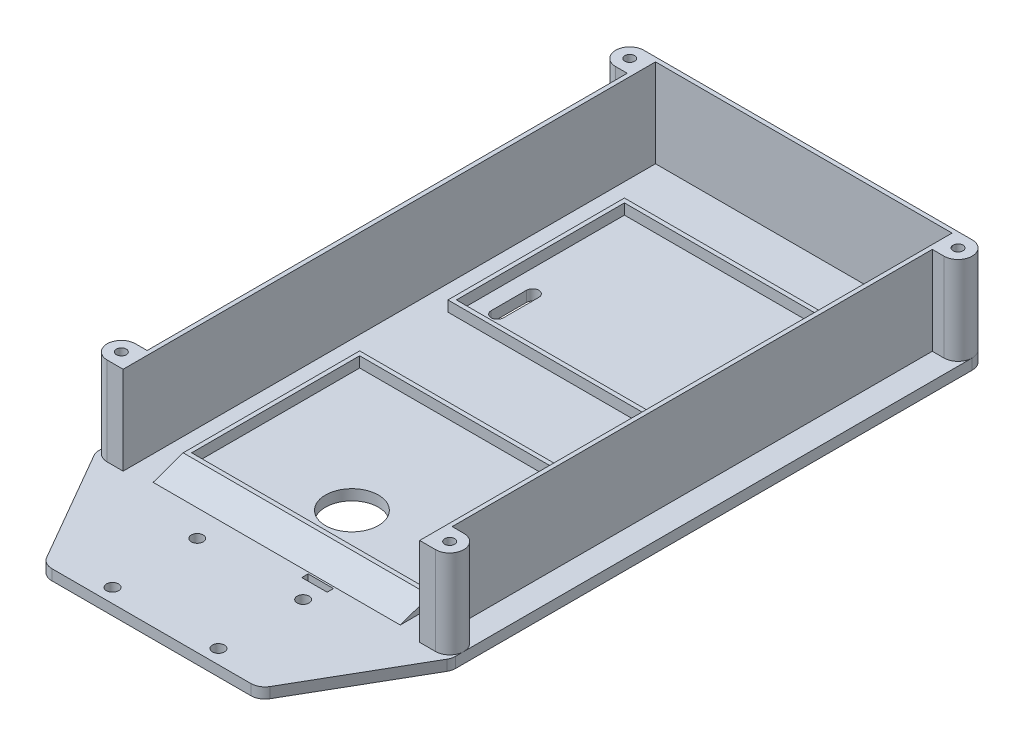
SolidWorks part; units mm, degrees
material "S235JR"
ref_plane "Piano X" through (0, 0, 0) normal (0, 0, 1) x (1, 0, 0)
ref_plane "Piano Y" through (0, 0, 0) normal (0, 1, 0) x (1, 0, 0)
ref_plane "Piano Z" through (0, 0, 0) normal (1, 0, 0) x (0, 0, -1)
sketch "Schizzo1" plane through (0, 0, 0) normal (0, 1, 0) x (1, 0, 0)
  line L1 (-50.5, -93) -> (50.5, -93)
  line L2 (-50.5, -93) -> (-50.5, 93)
  line L3 (-50.5, 93) -> (50.5, 93)
  line L4 (50.5, -93) -> (50.5, 93)
  line L5 (0, 93) -> (0, -93) construction
  line L6 (-50.5, 0) -> (50.5, 0) construction
  point P0 (0, 0)
  dimension "D2" = 101
  dimension "D3" = 186
extrude "Estrusione-Estrusione1" add sketch "Schizzo1" along normal blind 3
sketch "Schizzo3" plane through (0, 3, 0) normal (0, 1, 0) x (1, 0, 0)
  line L0 (-43.2, -59) -> (-42, -59)
  line L1 (42, 91.8) -> (-42, 91.8)
  line L2 (42, 91.8) -> (42, -59)
  line L4 (-42, 91.8) -> (-42, -59)
  line L5 (0, 86.851) -> (0, 91.8) construction
  line L6 (42, 16.4) -> (-42, 16.4) construction
  line L7 (43.2, 93) -> (-43.2, 93)
  line L8 (43.2, 93) -> (43.2, -59)
  line L10 (-43.2, 93) -> (-43.2, -59)
  line L11 (0, 88.051) -> (0, 93) construction
  line L12 (43.2, 16.4) -> (-43.2, 16.4) construction
  line L13 (42, -59) -> (43.2, -59)
  line L14 (-50.5, -93) -> (50.5, -93) construction
  point P0 (0, 16.4)
  point P4 (0, 16.4)
  point P11 (43.2, 75.8551)
  point P12 (0, 0)
  point P13 (-42, -72.5522)
  point P19 (0, 0)
  dimension "D1" = 84
  dimension "D2" = 1.2
  dimension "D3" = 1.2
  dimension "D4" = 34
  dimension "D5" = 152
extrude "Estrusione-Estrusione3" add sketch "Schizzo3" along normal blind 25
sketch "Schizzo2" plane through (0, 3, 0) normal (0, 1, 0) x (1, 0, 0)
  line L0 (0, 51) -> (0, -24) construction
  line L1 (35, 26) -> (-35, 26)
  line L2 (35, 26) -> (35, 76)
  line L3 (35, 76) -> (-35, 76)
  line L4 (-35, 26) -> (-35, 76)
  line L5 (0, 76) -> (0, 26) construction
  line L6 (35, 51) -> (-35, 51) construction
  line L7 (33.8, 27.2) -> (-33.8, 27.2)
  line L8 (33.8, 27.2) -> (33.8, 74.8)
  line L9 (33.8, 74.8) -> (-33.8, 74.8)
  line L10 (-33.8, 27.2) -> (-33.8, 74.8)
  line L11 (0, 74.8) -> (0, 27.2) construction
  line L12 (33.8, 51) -> (-33.8, 51) construction
  line L13 (33.8, -47.8) -> (-33.8, -47.8)
  line L14 (33.8, -47.8) -> (33.8, -0.2)
  line L15 (33.8, -0.2) -> (-33.8, -0.2)
  line L16 (-33.8, -47.8) -> (-33.8, -0.2)
  line L17 (0, -0.2) -> (0, -47.8) construction
  line L18 (33.8, -24) -> (-33.8, -24) construction
  line L19 (35, -49) -> (-35, -49)
  line L20 (35, -49) -> (35, 1)
  line L21 (35, 1) -> (-35, 1)
  line L22 (-35, -49) -> (-35, 1)
  line L23 (0, 1) -> (0, -49) construction
  line L24 (35, -24) -> (-35, -24) construction
  point P0 (0, 51)
  point P4 (0, 51)
  point P11 (0, -24)
  point P18 (0, -24)
  point P25 (15.7007, -24.3129)
  point P26 (0, 0)
  point P32 (0, 0)
  point P33 (0, 0)
  point P34 (0, 0)
  dimension "D1" = 1.2
  dimension "D2" = 1.2
  dimension "D3" = 70
  dimension "D4" = 50
  dimension "D5" = 10
  dimension "D6" = 25
extrude "Estrusione-Estrusione2" add sketch "Schizzo2" along normal blind 3
sketch "Schizzo13" plane through (-35, 0, 0) normal (-1, 0, 0) x (0, 0, 1)
  line L0 (49, 6) -> (57.5, 3)
  line L1 (57.5, 3) -> (49, 3)
  line L2 (49, 3) -> (49, 6)
  line L3 (-93, 3) -> (93, 3) construction
  line L4 (59, 28) -> (59, 3) construction
  point P4 (57.5991, 3)
  dimension "D1" = 1.5
extrude "Estrusione-Estrusione5" add sketch "Schizzo13" against normal up to surface (70 mm away) up to face at (35, 4.5, 24)
sketch "Schizzo9" plane through (0, 3, 0) normal (0, 1, 0) x (1, 0, 0)
  line L0 (-42, 91.8) -> (42, 91.8) construction
  circle A0 centre (0, -36.2) radius 7.5
  point P2 (0, 0)
  dimension "D1" = 15
  dimension "D2" = 128
extrude "Taglio-Estrusione2" cut sketch "Schizzo9" against normal through all both and the other way through all
sketch "Schizzo4" plane through (0, 3, 0) normal (0, 1, 0) x (1, 0, 0)
  line L1 (42, -59) -> (43.2, -59) construction
  line L2 (9.4, -59.8) -> (16.6, -59.8)
  line L3 (9.4, -59.8) -> (9.4, -58)
  line L4 (9.4, -58) -> (16.6, -58)
  line L5 (16.6, -59.8) -> (16.6, -58)
  line L6 (13, -58) -> (13, -59.8) construction
  line L7 (9.4, -58.9) -> (16.6, -58.9) construction
  circle A2 centre (0, -36.2) radius 7.5 construction
  point P0 (13, -58.9)
  dimension "D1" = 7.2
  dimension "D4" = 13
  dimension "D2" = 1.8
  dimension "D3" = 1
extrude "Taglio-Estrusione1" cut sketch "Schizzo4" against normal through all
sketch "Schizzo5" plane through (0, 3, 0) normal (0, 1, 0) x (1, 0, 0)
  line L0 (-43.2, 93) -> (-43.2, 85)
  line L1 (46.5, -55) -> (-46.5, -55) construction
  line L2 (46.5, -55) -> (46.5, 89) construction
  line L3 (46.5, 89) -> (-46.5, 89) construction
  line L4 (-46.5, -55) -> (-46.5, 89) construction
  line L5 (0, 89) -> (0, -55) construction
  line L6 (46.5, 17) -> (-46.5, 17) construction
  line L9 (-43.2, 93) -> (-43.2, -59) construction
  line L12 (46.5, 85) -> (43.2, 85)
  line L13 (43.2, -59) -> (43.2, 93) construction
  line L14 (46.5, 93) -> (43.2, 93)
  line L15 (43.2, -59) -> (43.2, 93) construction
  line L16 (43.2, 93) -> (43.2, 85)
  line L17 (46.5, -51) -> (43.2, -51)
  line L19 (43.2, -51) -> (43.2, -59)
  line L20 (43.2, -59) -> (46.5, -59)
  line L21 (-46.5, -51) -> (-43.2, -51)
  line L22 (-43.2, -51) -> (-43.2, -59)
  line L23 (-43.2, 93) -> (-43.2, -59) construction
  line L24 (-43.2, -59) -> (-46.5, -59)
  line L25 (-43.2, 85) -> (-46.5, 85)
  line L26 (-46.5, 93) -> (-43.2, 93)
  arc A0 (46.5, -59) -> (46.5, -51) centre (46.5, -55) ccw
  arc A1 (46.5, 85) -> (46.5, 93) centre (46.5, 89) ccw
  arc A3 (-46.5, -51) -> (-46.5, -59) centre (-46.5, -55) ccw
  arc A4 (-46.5, 85) -> (-46.5, 93) centre (-46.5, 89) cw
  point P7 (-43.4632, 92.7629)
  point P8 (0, 0)
  point P24 (0, 0)
  point P34 (-46.5, 89.5383)
  dimension "D1" = 8
  dimension "D2" = 93
extrude "Estrusione-Estrusione4" add sketch "Schizzo5" along normal blind 25
hole_wizard "Foro Ø2.8 (2.8)-1" positions "Schizzo6" profile "Schizzo8" hole size "Ø2.8" standard "ISO"
sketch "Schizzo6" plane through (0, 28, 0) normal (0, 1, 0) x (1, 0, 0)
  point P0 (-46.5, 89)
  point P3 (46.5, 89)
  point P6 (46.5, -55)
  point P9 (-46.5, -55)
  point P13 (-46.5, 89)
sketch "Schizzo8" plane through (-46.5, 28, -89) normal (1, 0, 0) x (0, 0, 1)
  line L0 (0, 0) -> (0, 10.8412)
  line L1 (0, 10.8412) -> (1.4, 10)
  line L2 (1.4, 10) -> (1.4, 0)
  line L5 (1.4, 0) -> (0, 0)
  line L10 (0, 10.8412) -> (-1.4, 10) construction
  line L11 (0, -6.35) -> (0, 107.95) construction
  dimension "Hole Dia." = 2.8
  dimension "Hole Depth" = 10
  dimension "Drill Angle" = 118
chamfer "Smusso1" distance 20 angle 60 2 edges at (50.5, 1.5, 93) (-50.5, 1.5, 93) first distance on face at (0, 1.5, 93)
fillet "Raccordo1" radius 4 6 edges at (50.5, 1.5, 58.359) (-50.5, 1.5, 58.359) (30.5, 1.5, 93) (-30.5, 1.5, 93) (-50.5, 1.5, -93) (50.5, 1.5, -93)
sketch "Schizzo10" plane through (0, 3, 0) normal (0, 1, 0) x (1, 0, 0)
  line L0 (27.5, 42.5) -> (27.5, 32.5) construction
  line L1 (29.25, 42.5) -> (29.25, 32.5)
  line L2 (25.75, 42.5) -> (25.75, 32.5)
  line L3 (-27.5, 42.5) -> (-27.5, 32.5) construction
  line L4 (-25.75, 42.5) -> (-25.75, 32.5)
  line L5 (-29.25, 42.5) -> (-29.25, 32.5)
  line L6 (-27.5, 37.5) -> (27.5, 37.5) construction
  line L7 (0, 37.5) -> (0, 0) construction
  line L9 (50.5, -55) -> (50.5, 89) construction
  line L10 (46.5, 93) -> (-46.5, 93) construction
  arc A0 (29.25, 42.5) -> (25.75, 42.5) centre (27.5, 42.5) ccw
  arc A1 (25.75, 32.5) -> (29.25, 32.5) centre (27.5, 32.5) ccw
  arc A2 (-25.75, 42.5) -> (-29.25, 42.5) centre (-27.5, 42.5) ccw
  arc A3 (-29.25, 32.5) -> (-25.75, 32.5) centre (-27.5, 32.5) ccw
  point P2 (27.5, 37.5)
  point P8 (-27.5, 37.5)
  dimension "D1" = 23
  dimension "D2" = 3.5
  dimension "D3" = 10
  dimension "D4" = 55.5
extrude "Taglio-Estrusione3" cut sketch "Schizzo10" against normal through all
hole_wizard "Foro per Vite M3-1" positions "Schizzo11" profile "Schizzo12" hole size "M3" standard "ISO"
sketch "Schizzo11" plane through (0, 3, 0) normal (0, 1, 0) x (1, 0, 0)
  point P0 (15, -65)
  point P3 (15, -89)
  point P6 (-15, -89)
  point P9 (-15, -65)
sketch "Schizzo12" plane through (15, 3, 65) normal (1, 0, 0) x (0, 0, 1)
  line L0 (0, 0) -> (0, 11.0215)
  line L1 (0, 11.0215) -> (1.7, 10)
  line L2 (1.7, 10) -> (1.7, 0)
  line L5 (1.7, 0) -> (0, 0)
  line L10 (0, 11.0215) -> (-1.7, 10) construction
  line L11 (0, -6.35) -> (0, 107.95) construction
  dimension "Hole Dia." = 3.4
  dimension "Hole Depth" = 10
  dimension "Drill Angle" = 118
